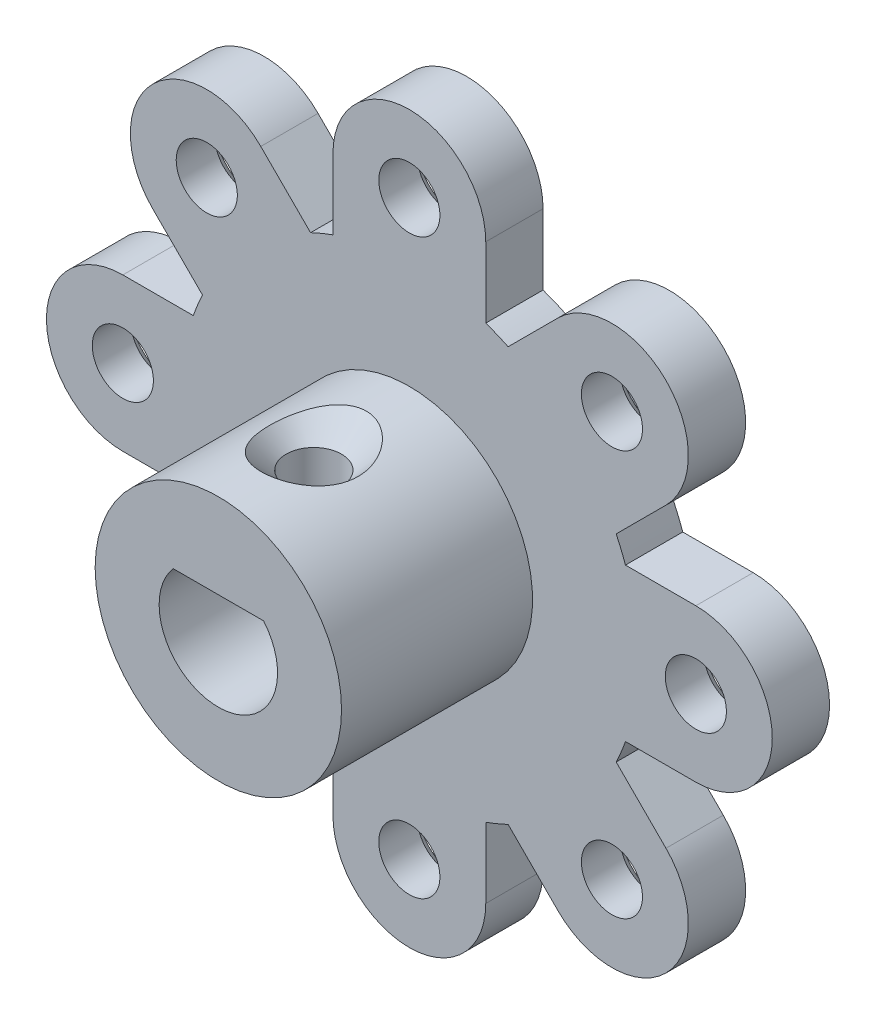
SolidWorks part; units mm, degrees
ref_plane "Front Plane" through (0, 0, 0) normal (0, 0, 1) x (1, 0, 0)
ref_plane "Top Plane" through (0, 0, 0) normal (0, 1, 0) x (1, 0, 0)
ref_plane "Right Plane" through (0, 0, 0) normal (1, 0, 0) x (0, 0, -1)
ref_axis "Axe1" through (0, 0, 11.8837) along (0, 0, -1)
sketch "Esquisse1" plane through (0, 0, 0) normal (0, 0, 1) x (1, 0, 0)
  line L0 (11.3137, 4) -> (15, 4)
  line L1 (11.3137, -4) -> (15, -4)
  line L2 (0, 0) -> (11.0866, 4.5922)
  line L3 (0, 0) -> (11.0866, -4.5922)
  line L4 (0, 0) -> (15, 0) construction
  arc A0 (11.0866, 4.5922) -> (11.3137, 4) centre (0, 0) cw
  arc A1 (11.0866, -4.5922) -> (11.3137, -4) centre (0, 0) ccw
  arc A2 (15, -4) -> (15, 4) centre (15, 0) ccw
  dimension "D1" = 12
  dimension "D2" = 8
  dimension "D3" = 15
  dimension "D4" = 22.5
  dimension "D5" = 22.5
extrude "Main" add sketch "Esquisse1" along normal blind 3
pattern_circular "Répétition circulaire1" count 8 every 45 about axis through (0, 0, 11.8837) along (0, 0, -1) of "Main"
sketch "Esquisse2" plane through (0, 0, 3) normal (0, 0, 1) x (1, 0, 0)
  circle A0 centre (0, 0) radius 3.1
  circle A1 centre (0, 0) radius 6.45
  dimension "D1" = 6.2
  dimension "D2" = 12.9
extrude "MotorLink" add sketch "Esquisse2" along normal blind 10
sketch "Esquisse3" plane through (0, 0, 3) normal (0, 0, 1) x (1, 0, 0)
  line L0 (-2.3685, 2) -> (2.3685, 2)
  circle A0 centre (0, 0) radius 3.1 construction
  arc A1 (2.3685, 2) -> (-2.3685, 2) centre (0, 0) ccw
  dimension "D1" = 2
extrude "Meplat" add sketch "Esquisse3" along normal blind 10
sketch "Esquisse4" plane through (0, 0, 3) normal (0, 0, 1) x (1, 0, 0)
  circle A0 centre (0, 0) radius 3.1
  circle A1 centre (0, 0) radius 3.1 construction
extrude "Hole" cut sketch "Esquisse4" against normal through all
sketch "Esquisse5" plane through (0, 0, 0) normal (0, 0, -1) x (-1, 0, 0)
  circle A0 centre (0, 0) radius 3.1
  circle A1 centre (0, 0) radius 4
  circle A2 centre (0, 0) radius 3.1 construction
  dimension "D1" = 8
extrude "RollingBearingLink" add sketch "Esquisse5" along normal blind 7
sketch "Esquisse6" plane through (0, 0, 0) normal (0, 0, -1) x (-1, 0, 0)
  circle A0 centre (0, 0) radius 5
  circle A1 centre (0, 0) radius 4
  circle A2 centre (0, 0) radius 4 construction
  dimension "D1" = 10
extrude "RollingBearLink2" add sketch "Esquisse6" along normal blind 0.5
hole_wizard "Fraisage pour vis à tête fraisée (100) #01" positions "Esquisse9" profile "Esquisse10" countersink size "#0" standard "Ansi Inch" end condition through all
sketch "Esquisse9" plane through (0, 0, 0) normal (0, 0, -1) x (-1, 0, 0)
  arc A1 (15, -4) -> (15, 4) centre (15, 0) ccw construction
  point P0 (15, 0)
sketch "Esquisse10" plane through (-15, 0, 0) normal (1, 0, 0) x (0, 1, 0)
  line L0 (0, 0) -> (0, 13)
  line L1 (0, 13) -> (1.6, 13)
  line L2 (1.6, 13) -> (1.6, 0.965)
  line L3 (1.6, 0.965) -> (2.75, 0)
  line L5 (2.75, 0) -> (0, 0)
  line L6 (-1.6, 0.965) -> (-2.75, 0) construction
  line L11 (0, -6.35) -> (0, 107.95) construction
  dimension "Diamètre du perçage jusqu'au prochain" = 3.2
  dimension "Profondeur du perçage jusqu'au prochain" = 13
  dimension "Diamètre du fraisage entrant" = 5.5
  dimension "Angle du fraisage entrant" = 100
pattern_circular "Répétition circulaire2" count 8 every 45 about axis through (0, 0, 11.8837) along (0, 0, -1) of "Fraisage pour vis à tête fraisée (100) #01"
ref_plane "Plane1" through (0, 6.45, 0) normal (0, 1, 0) x (1, 0, 0)
hole_wizard "CSK for M2.5 Flat Head Machine Screw1" positions "Sketch3" profile "Sketch2" countersink size "M2.5" standard "ANSI Metric" end condition through all
sketch "Sketch3" plane through (0, 6.45, 0) normal (0, 1, 0) x (1, 0, 0)
  line L0 (0, -11.8837) -> (0, 8.879) construction
  line L1 (-6.45, -13) -> (6.45, -13) construction
  point P0 (0, -8)
  point P1 (0, -9.6157)
  dimension "D1" = 5
sketch "Sketch2" plane through (0, 6.45, 8) normal (1, 0, 0) x (0, 0, 1)
  line L0 (0, 0) -> (0, 25.45)
  line L1 (0, 25.45) -> (1.45, 25.45)
  line L2 (1.45, 25.45) -> (1.45, 1.3)
  line L3 (1.45, 1.3) -> (2.75, 0)
  line L5 (2.75, 0) -> (0, 0)
  line L6 (-1.45, 1.3) -> (-2.75, 0) construction
  line L11 (0, -6.35) -> (0, 107.95) construction
  dimension "Thru Hole Dia." = 2.9
  dimension "Thru Hole Depth" = 25.45
  dimension "Near C'Sink Dia." = 5.5
  dimension "Near C'Sink Angle" = 90
